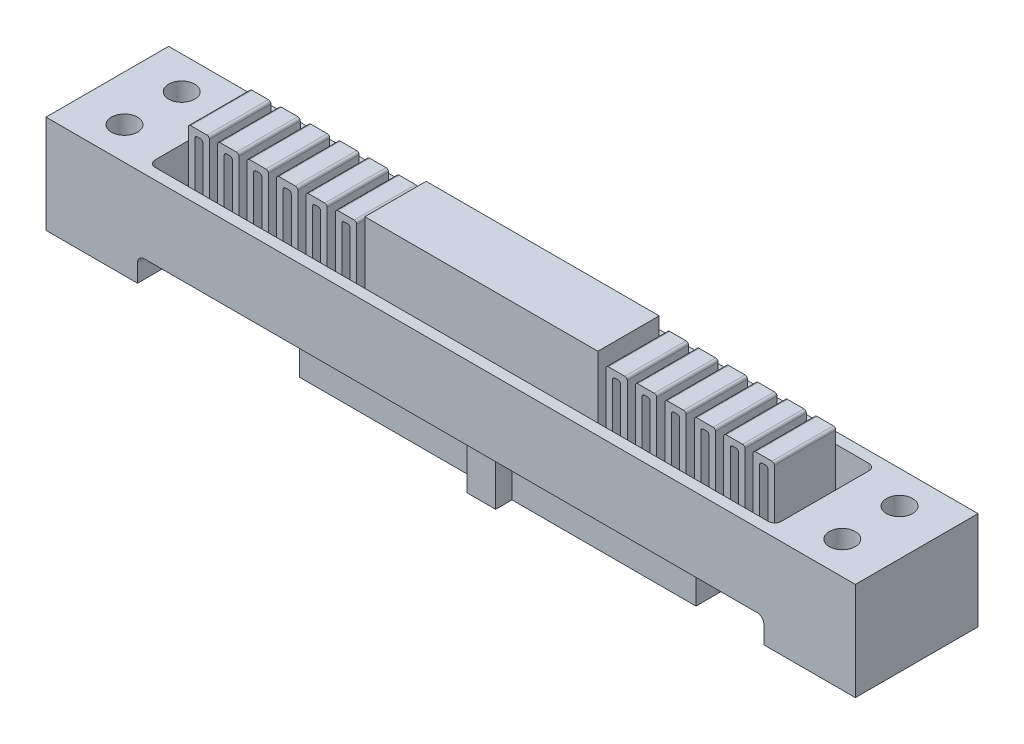
SolidWorks part; units mm, degrees
ref_plane "前视基准面" through (0, 0, 0) normal (0, 0, 1) x (1, 0, 0)
ref_plane "上视基准面" through (0, 0, 0) normal (0, 1, 0) x (1, 0, 0)
ref_plane "右视基准面" through (0, 0, 0) normal (1, 0, 0) x (0, 0, -1)
sketch "草图1" plane through (0, 0, 0) normal (0, 1, 0) x (1, 0, 0)
  line L0 (-1.75, 1.75) -> (-24.25, 1.75)
  line L1 (1.75, -3.75) -> (-1.75, -3.75)
  line L2 (1.75, -3.75) -> (1.75, -1.75)
  line L3 (1.75, 3.75) -> (-1.75, 3.75)
  line L4 (-1.75, -3.75) -> (-1.75, -1.75)
  line L5 (1.75, -3.75) -> (-1.75, 3.75) construction
  line L6 (1.75, 3.75) -> (-1.75, -3.75) construction
  line L7 (24.25, -1.75) -> (1.75, -1.75)
  line L8 (24.25, -1.75) -> (24.25, 1.75)
  line L9 (24.25, 1.75) -> (1.75, 1.75)
  line L10 (-24.25, -1.75) -> (-24.25, 1.75)
  line L11 (24.25, -1.75) -> (-24.25, 1.75) construction
  line L12 (24.25, 1.75) -> (-24.25, -1.75) construction
  line L13 (1.75, 1.75) -> (1.75, 3.75)
  line L14 (-1.75, -1.75) -> (-24.25, -1.75)
  line L15 (-1.75, 1.75) -> (-1.75, 3.75)
  point P0 (0, 0)
  point P6 (0, 0)
  dimension "D1" = 7.5
  dimension "D2" = 3.5
  dimension "D3" = 48.5
  dimension "D4" = 3.5
extrude "凸台-拉伸1" add sketch "草图1" along normal blind 23
ref_plane "基准面4" through (0, 5.8, 0) normal (0, -1, 0) x (-1, 0, 0)
ref_plane "基准面5" through (0, 8.8, 0) normal (0, -1, 0) x (-1, 0, 0)
sketch "草图3" plane through (0, 8.8, 0) normal (0, -1, 0) x (-1, 0, 0)
  line L0 (-14.25, 1.75) -> (-14.25, -1.75)
  line L1 (14.25, 1.75) -> (14.25, -1.75)
  line L12 (1.75, 1.75) -> (1.75, 3.75)
  line L13 (1.75, 3.75) -> (-1.75, 3.75)
  line L14 (-1.75, 3.75) -> (-1.75, 1.75)
  line L15 (-1.75, 1.75) -> (-24.25, 1.75)
  line L16 (-24.25, 1.75) -> (-24.25, -1.75)
  line L17 (-24.25, -1.75) -> (-1.75, -1.75)
  line L18 (-1.75, -1.75) -> (-1.75, -3.75)
  line L19 (-1.75, -3.75) -> (1.75, -3.75)
  line L20 (1.75, -3.75) -> (1.75, -1.75)
  line L21 (1.75, -1.75) -> (24.25, -1.75)
  line L22 (24.25, -1.75) -> (24.25, 1.75)
  line L23 (24.25, 1.75) -> (1.75, 1.75)
  line L27 (-14.25, 1.75) -> (-24.25, 1.75)
  line L28 (-24.25, 1.75) -> (-24.25, -1.75)
  line L29 (-24.25, -1.75) -> (-14.25, -1.75)
  line L33 (14.25, -1.75) -> (24.25, -1.75)
  line L34 (24.25, -1.75) -> (24.25, 1.75)
  line L35 (24.25, 1.75) -> (14.25, 1.75)
  dimension "D2" = 10
  dimension "D3" = 10
  dimension "D1" = 0
extrude "切除-拉伸1" cut sketch "草图3" against normal up to next
sketch "草图4" plane through (0, 0, 1.75) normal (0, 0, 1) x (1, 0, 0)
  line L0 (14.25, 11.2) -> (16.05, 11.2)
  line L1 (14.25, 23) -> (14.25, 8.8) construction
  line L2 (16.05, 11.2) -> (16.05, 21.2)
  line L3 (16.05, 21.2) -> (17.05, 21.2)
  line L4 (17.05, 21.2) -> (17.05, 11.2)
  line L5 (24.25, 8.8) -> (14.25, 8.8) construction
  line L6 (14.25, 12) -> (15.25, 12)
  line L7 (15.25, 12) -> (15.25, 22)
  line L8 (15.25, 22) -> (17.85, 22)
  line L9 (17.85, 22) -> (17.85, 12)
  line L10 (17.05, 11.2) -> (17.85, 11.2)
  line L11 (14.25, 12) -> (14.25, 11.2)
  line L12 (17.85, 22) -> (17.85, 11.2) construction
  line L13 (17.85, 11.2) -> (19.65, 11.2)
  line L14 (17.85, 12) -> (18.85, 12)
  line L15 (18.85, 12) -> (18.85, 22)
  line L16 (18.85, 22) -> (21.45, 22)
  line L17 (21.45, 22) -> (21.45, 12)
  line L18 (19.65, 21.2) -> (20.65, 21.2)
  line L19 (19.65, 11.2) -> (19.65, 21.2)
  line L20 (20.65, 21.2) -> (20.65, 11.2)
  line L21 (20.65, 11.2) -> (21.45, 11.2)
  line L22 (21.45, 11.2) -> (23.25, 11.2)
  line L23 (21.45, 12) -> (22.45, 12)
  line L24 (22.45, 12) -> (22.45, 22)
  line L25 (22.45, 22) -> (25.05, 22)
  line L26 (25.05, 22) -> (25.05, 12)
  line L27 (23.25, 21.2) -> (24.25, 21.2)
  line L28 (23.25, 11.2) -> (23.25, 21.2)
  line L29 (24.25, 21.2) -> (24.25, 11.2)
  line L30 (24.25, 11.2) -> (25.05, 11.2)
  line L31 (25.05, 11.2) -> (26.85, 11.2)
  line L32 (25.05, 12) -> (26.05, 12)
  line L33 (26.05, 12) -> (26.05, 22)
  line L34 (26.05, 22) -> (28.65, 22)
  line L35 (28.65, 22) -> (28.65, 12)
  line L36 (26.85, 21.2) -> (27.85, 21.2)
  line L37 (26.85, 11.2) -> (26.85, 21.2)
  line L38 (27.85, 21.2) -> (27.85, 11.2)
  line L39 (27.85, 11.2) -> (28.65, 11.2)
  line L40 (28.65, 11.2) -> (30.45, 11.2)
  line L41 (28.65, 12) -> (29.65, 12)
  line L42 (29.65, 12) -> (29.65, 22)
  line L43 (29.65, 22) -> (32.25, 22)
  line L44 (32.25, 22) -> (32.25, 12)
  line L45 (30.45, 21.2) -> (31.45, 21.2)
  line L46 (30.45, 11.2) -> (30.45, 21.2)
  line L47 (31.45, 21.2) -> (31.45, 11.2)
  line L48 (31.45, 11.2) -> (32.25, 11.2)
  line L49 (32.25, 11.2) -> (34.05, 11.2)
  line L50 (32.25, 12) -> (33.25, 12)
  line L51 (33.25, 12) -> (33.25, 22)
  line L52 (33.25, 22) -> (35.85, 22)
  line L53 (35.85, 22) -> (35.85, 12)
  line L54 (34.05, 21.2) -> (35.05, 21.2)
  line L55 (34.05, 11.2) -> (34.05, 21.2)
  line L56 (35.05, 21.2) -> (35.05, 11.2)
  line L57 (35.05, 11.2) -> (35.85, 11.2)
  line L58 (35.85, 11.2) -> (37.65, 11.2)
  line L59 (35.85, 12) -> (36.85, 12)
  line L60 (36.85, 12) -> (36.85, 22)
  line L61 (36.85, 22) -> (39.45, 22)
  line L62 (39.45, 22) -> (39.45, 12)
  line L63 (37.65, 21.2) -> (38.65, 21.2)
  line L64 (37.65, 11.2) -> (37.65, 21.2)
  line L65 (38.65, 21.2) -> (38.65, 11.2)
  line L66 (38.65, 11.2) -> (39.45, 11.2)
  line L67 (39.45, 11.2) -> (41.25, 11.2)
  line L68 (39.45, 12) -> (40.45, 12)
  line L69 (40.45, 12) -> (40.45, 22)
  line L70 (40.45, 22) -> (43.05, 22)
  line L71 (43.05, 22) -> (43.05, 12)
  line L72 (41.25, 21.2) -> (42.25, 21.2)
  line L73 (41.25, 11.2) -> (41.25, 21.2)
  line L74 (42.25, 21.2) -> (42.25, 11.2)
  line L75 (42.25, 11.2) -> (43.05, 11.2)
  line L76 (43.05, 11.2) -> (44.85, 11.2)
  line L77 (43.05, 12) -> (44.05, 12)
  line L78 (44.05, 12) -> (44.05, 22)
  line L79 (44.05, 22) -> (46.65, 22)
  line L80 (46.65, 22) -> (46.65, 12)
  line L81 (44.85, 21.2) -> (45.85, 21.2)
  line L82 (44.85, 11.2) -> (44.85, 21.2)
  line L83 (45.85, 21.2) -> (45.85, 11.2)
  line L84 (45.85, 11.2) -> (46.65, 11.2)
  line L85 (46.65, 11.2) -> (48.45, 11.2)
  line L86 (46.65, 12) -> (47.65, 12)
  line L87 (47.65, 12) -> (47.65, 22)
  line L88 (47.65, 22) -> (50.25, 22)
  line L89 (50.25, 22) -> (50.25, 12)
  line L90 (48.45, 21.2) -> (49.45, 21.2)
  line L91 (48.45, 11.2) -> (48.45, 21.2)
  line L92 (49.45, 21.2) -> (49.45, 11.2)
  line L93 (49.45, 11.2) -> (50.25, 11.2)
  line L94 (14.25, 11.2) -> (17.85, 11.2) construction
  line L95 (50.25, 11.2) -> (50.25, 12)
  dimension "D1" = 1.8
  dimension "D2" = 1
  dimension "D3" = 10
  dimension "D4" = 10
  dimension "D5" = 2.4
  dimension "D7" = 10
  dimension "D9" = 3.6
  dimension "D6" = 0.8
  dimension "D8" = 10
extrude "凸台-拉伸3" add sketch "草图4" against normal up to surface (3.5 mm away) contours L93 L95 L89 L88 L87 L86 L80 L79 L78 L77 L71 L70 L69 L68 L62 L61 L60 L59 L53 L52 L51 L50 L44 L43 L42 L41 L35 L34 L33 L32 L26 L25 L24 L23 L17 L16 L15 L14 L9 L8 L7 L6 L5 L0 L2 L3 L4 L10 L13 L19 L18 region at (14.6259, 11.6, 1.75) up to face at (13.4167, 10.6, -1.75)
fillet "圆角1" radius 0.3 78 edges at (45.85, 11.2, 0) (44.85, 11.2, 0) (42.25, 11.2, 0) (41.25, 11.2, 0) (38.65, 11.2, 0) (44.05, 12, 0) (40.45, 12, 0) (39.45, 12, 0) (43.05, 12, 0) (46.65, 12, 0) (47.65, 12, 0) (48.45, 11.2, 0) (48.45, 21.2, 0) (49.45, 21.2, 0) (45.85, 21.2, 0) (44.85, 21.2, 0) (41.25, 21.2, 0) (42.25, 21.2, 0) (38.65, 21.2, 0) (37.65, 21.2, 0) (50.25, 22, 0) (47.65, 22, 0) (46.65, 22, 0) (44.05, 22, 0) (43.05, 22, 0) (40.45, 22, 0) (39.45, 22, 0) (36.85, 22, 0) (37.65, 11.2, 0) (36.85, 12, 0) (35.85, 12, 0) (35.05, 11.2, 0) (35.05, 21.2, 0) (34.05, 21.2, 0) (35.85, 22, 0) (33.25, 22, 0) (33.25, 12, 0) (34.05, 11.2, 0) (32.25, 12, 0) (31.45, 11.2, 0) (31.45, 21.2, 0) (32.25, 22, 0) (30.45, 21.2, 0) (29.65, 22, 0) (29.65, 12, 0) (30.45, 11.2, 0) (28.65, 12, 0) (27.85, 11.2, 0) (27.85, 21.2, 0) (28.65, 22, 0) (26.85, 21.2, 0) (26.05, 22, 0) (26.05, 12, 0) (26.85, 11.2, 0) (25.05, 12, 0) (24.25, 11.2, 0) (24.25, 21.2, 0) (25.05, 22, 0) (22.45, 22, 0) (23.25, 21.2, 0) (23.25, 11.2, 0) (22.45, 12, 0) (20.65, 11.2, 0) (21.45, 12, 0) (21.45, 22, 0) (20.65, 21.2, 0) (19.65, 21.2, 0) (18.85, 22, 0) (19.65, 11.2, 0) (18.85, 12, 0) (17.85, 12, 0) (17.05, 11.2, 0) (16.05, 11.2, 0) (15.25, 12, 0) (17.05, 21.2, 0) (16.05, 21.2, 0) (17.85, 22, 0) (15.25, 22, 0)
mirror "镜向2" about plane through (0, 0, 0) normal (1, 0, 0) of "凸台-拉伸3", "圆角1"
fillet "圆角2" radius 0.3 4 edges at (-14.25, 12, 0) (-14.25, 11.2, 0) (14.25, 12, 0) (14.25, 11.2, 0)
ref_plane "基准面6" through (38.3, 0, 0) normal (1, 0, 0) x (0, 0, -1)
sketch "草图6" plane through (38.3, 0, 0) normal (1, 0, 0) x (0, 0, -1)
  line L0 (3.75, 23) -> (3.75, 0) construction
  line L1 (3.75, 0) -> (-3.75, 0)
  line L2 (3.75, 0) -> (3.75, 23)
  line L3 (3.75, 23) -> (-3.75, 23)
  line L4 (-3.75, 0) -> (-3.75, 23)
  dimension "D1" = 23
extrude "切除-拉伸2" cut sketch "草图6" along normal up to next
extrude "切除-拉伸3" cut sketch "草图6<2>" against normal blind 1.8
sketch "草图6<2>" plane through (38.3, 0, 0) normal (1, 0, 0) x (0, 0, -1) same geometry as "草图6"
sketch "草图7" plane through (36.5, 0, 0) normal (1, 0, 0) x (0, 0, -1)
  line L4 (1.75, 11.2) -> (1.75, 12)
  line L5 (1.75, 12) -> (-1.75, 12)
  line L6 (-1.75, 12) -> (-1.75, 11.2)
  line L7 (-1.75, 11.2) -> (1.75, 11.2)
  line L8 (1.75, 11.2) -> (1.75, 12)
  line L9 (1.75, 12) -> (-1.75, 12)
  line L10 (-1.75, 12) -> (-1.75, 11.2)
  line L11 (-1.75, 11.2) -> (1.75, 11.2)
  dimension "D1" = 0
extrude "凸台-拉伸4" add sketch "草图7" along normal up to surface (1.8 mm away) up to plane "基准面6"
mirror "镜向5" about plane through (0, 0, 0) normal (1, 0, 0) of "切除-拉伸3", "切除-拉伸2"
ref_plane "基准面7" through (-38.3, 0, 0) normal (-1, 0, 0) x (0, 0, 1)
sketch "草图16" plane through (-36.5, 0, 0) normal (-1, 0, 0) x (0, 0, 1)
  line L4 (-1.75, 11.2) -> (1.75, 11.2)
  line L5 (1.75, 11.2) -> (1.75, 12)
  line L6 (1.75, 12) -> (-1.75, 12)
  line L7 (-1.75, 12) -> (-1.75, 11.2)
  line L8 (-1.75, 11.2) -> (1.75, 11.2)
  line L9 (1.75, 11.2) -> (1.75, 12)
  line L10 (1.75, 12) -> (-1.75, 12)
  line L11 (-1.75, 12) -> (-1.75, 11.2)
  dimension "D1" = 0
extrude "凸台-拉伸8" add sketch "草图16" along normal up to surface (1.8 mm away) up to plane "基准面7"
sketch "草图12" plane through (0, 5.8, 0) normal (0, -1, 0) x (-1, 0, 0)
  line L0 (-24.25, -1.75) -> (-24.25, 1.75) construction
  line L1 (-49.5, -7.5) -> (-38.3, -7.5)
  line L2 (-49.5, -7.5) -> (-49.5, 7.5)
  line L3 (-49.5, 7.5) -> (-38.3, 7.5)
  line L4 (-38.3, -7.5) -> (-38.3, 7.5)
  line L5 (-49.5, -7.5) -> (-38.3, 7.5) construction
  line L6 (-49.5, 7.5) -> (-38.3, -7.5) construction
  point P0 (-43.9, 0)
  dimension "D1" = 14.05
  dimension "D2" = 11.2
  dimension "D3" = 15
extrude "凸台-拉伸7" add sketch "草图12" against normal blind 12
sketch "草图14" plane through (0, 17.8, 0) normal (0, 1, 0) x (1, 0, 0)
  line L0 (43.9, 7.5) -> (43.9, -7.5) construction
  line L1 (38.3, 7.5) -> (49.5, 7.5) construction
  line L2 (49.5, -7.5) -> (38.3, -7.5) construction
  circle A0 centre (43.9, 3.5) radius 1.6
  circle A1 centre (43.9, -3.5) radius 1.6
  dimension "D1" = 3.2
  dimension "D2" = 3.2
  dimension "D3" = 4
  dimension "D4" = 4
extrude "切除-拉伸5" cut sketch "草图14" against normal up to next
mirror "镜向7" about plane through (0, 0, 0) normal (1, 0, 0) of "切除-拉伸5", "凸台-拉伸7"
sketch "草图18" plane through (0, 0, 1.75) normal (0, 0, 1) x (1, 0, 0)
  line L0 (-14.25, 8.8) -> (-1.75, 8.8)
  line L58 (-36.15, 12) -> (-38.3, 12)
  line L59 (-38.3, 12) -> (-38.3, 11.2)
  line L60 (-38.3, 11.2) -> (-35.35, 11.2)
  line L61 (-35.05, 11.5) -> (-35.05, 20.9)
  line L62 (-34.75, 21.2) -> (-34.35, 21.2)
  line L63 (-34.05, 20.9) -> (-34.05, 11.5)
  line L64 (-33.75, 11.2) -> (-31.75, 11.2)
  line L65 (-31.45, 11.5) -> (-31.45, 20.9)
  line L66 (-31.15, 21.2) -> (-30.75, 21.2)
  line L67 (-30.45, 20.9) -> (-30.45, 11.5)
  line L68 (-30.15, 11.2) -> (-28.15, 11.2)
  line L69 (-27.85, 11.5) -> (-27.85, 20.9)
  line L70 (-27.55, 21.2) -> (-27.15, 21.2)
  line L71 (-26.85, 20.9) -> (-26.85, 11.5)
  line L72 (-26.55, 11.2) -> (-24.55, 11.2)
  line L73 (-24.25, 11.5) -> (-24.25, 20.9)
  line L74 (-23.95, 21.2) -> (-23.55, 21.2)
  line L75 (-23.25, 20.9) -> (-23.25, 11.5)
  line L76 (-22.95, 11.2) -> (-20.95, 11.2)
  line L77 (-20.65, 11.5) -> (-20.65, 20.9)
  line L78 (-20.35, 21.2) -> (-19.95, 21.2)
  line L79 (-19.65, 20.9) -> (-19.65, 11.5)
  line L80 (-19.35, 11.2) -> (-17.35, 11.2)
  line L81 (-17.05, 11.5) -> (-17.05, 20.9)
  line L82 (-16.75, 21.2) -> (-16.35, 21.2)
  line L83 (-16.05, 20.9) -> (-16.05, 11.5)
  line L84 (-15.75, 11.2) -> (-14.55, 11.2)
  line L85 (-14.25, 10.9) -> (-14.25, 8.8)
  line L86 (-14.25, 8.8) -> (-24.25, 8.8)
  line L87 (-24.25, 8.8) -> (-24.25, 0)
  line L88 (-24.25, 0) -> (-1.75, 0)
  line L89 (-1.75, 0) -> (-1.75, 23)
  line L90 (-1.75, 23) -> (-14.25, 23)
  line L91 (-14.25, 23) -> (-14.25, 12.3)
  line L92 (-14.55, 12) -> (-14.95, 12)
  line L93 (-15.25, 12.3) -> (-15.25, 21.7)
  line L94 (-15.55, 22) -> (-17.55, 22)
  line L95 (-17.85, 21.7) -> (-17.85, 12.3)
  line L96 (-18.15, 12) -> (-18.55, 12)
  line L97 (-18.85, 12.3) -> (-18.85, 21.7)
  line L98 (-19.15, 22) -> (-21.15, 22)
  line L99 (-21.45, 21.7) -> (-21.45, 12.3)
  line L100 (-21.75, 12) -> (-22.15, 12)
  line L101 (-22.45, 12.3) -> (-22.45, 21.7)
  line L102 (-22.75, 22) -> (-24.75, 22)
  line L103 (-25.05, 21.7) -> (-25.05, 12.3)
  line L104 (-25.35, 12) -> (-25.75, 12)
  line L105 (-26.05, 12.3) -> (-26.05, 21.7)
  line L106 (-26.35, 22) -> (-28.35, 22)
  line L107 (-28.65, 21.7) -> (-28.65, 12.3)
  line L108 (-28.95, 12) -> (-29.35, 12)
  line L109 (-29.65, 12.3) -> (-29.65, 21.7)
  line L110 (-29.95, 22) -> (-31.95, 22)
  line L111 (-32.25, 21.7) -> (-32.25, 12.3)
  line L112 (-32.55, 12) -> (-32.95, 12)
  line L113 (-33.25, 12.3) -> (-33.25, 21.7)
  line L114 (-33.55, 22) -> (-35.55, 22)
  line L115 (-35.85, 21.7) -> (-35.85, 12.3)
  line L116 (-36.15, 12) -> (-38.3, 12)
  line L117 (-38.3, 12) -> (-38.3, 11.2)
  line L118 (-38.3, 11.2) -> (-35.35, 11.2)
  line L119 (-35.05, 11.5) -> (-35.05, 20.9)
  line L120 (-34.75, 21.2) -> (-34.35, 21.2)
  line L121 (-34.05, 20.9) -> (-34.05, 11.5)
  line L122 (-33.75, 11.2) -> (-31.75, 11.2)
  line L123 (-31.45, 11.5) -> (-31.45, 20.9)
  line L124 (-31.15, 21.2) -> (-30.75, 21.2)
  line L125 (-30.45, 20.9) -> (-30.45, 11.5)
  line L126 (-30.15, 11.2) -> (-28.15, 11.2)
  line L127 (-27.85, 11.5) -> (-27.85, 20.9)
  line L128 (-27.55, 21.2) -> (-27.15, 21.2)
  line L129 (-26.85, 20.9) -> (-26.85, 11.5)
  line L130 (-26.55, 11.2) -> (-24.55, 11.2)
  line L131 (-24.25, 11.5) -> (-24.25, 20.9)
  line L132 (-23.95, 21.2) -> (-23.55, 21.2)
  line L133 (-23.25, 20.9) -> (-23.25, 11.5)
  line L134 (-22.95, 11.2) -> (-20.95, 11.2)
  line L135 (-20.65, 11.5) -> (-20.65, 20.9)
  line L136 (-20.35, 21.2) -> (-19.95, 21.2)
  line L137 (-19.65, 20.9) -> (-19.65, 11.5)
  line L138 (-19.35, 11.2) -> (-17.35, 11.2)
  line L139 (-17.05, 11.5) -> (-17.05, 20.9)
  line L140 (-16.75, 21.2) -> (-16.35, 21.2)
  line L141 (-16.05, 20.9) -> (-16.05, 11.5)
  line L142 (-15.75, 11.2) -> (-14.55, 11.2)
  line L143 (-14.25, 10.9) -> (-14.25, 8.8)
  line L147 (-1.75, 8.8) -> (-1.75, 23)
  line L148 (-1.75, 23) -> (-14.25, 23)
  line L149 (-14.25, 23) -> (-14.25, 12.3)
  line L150 (-14.55, 12) -> (-14.95, 12)
  line L151 (-15.25, 12.3) -> (-15.25, 21.7)
  line L152 (-15.55, 22) -> (-17.55, 22)
  line L153 (-17.85, 21.7) -> (-17.85, 12.3)
  line L154 (-18.15, 12) -> (-18.55, 12)
  line L155 (-18.85, 12.3) -> (-18.85, 21.7)
  line L156 (-19.15, 22) -> (-21.15, 22)
  line L157 (-21.45, 21.7) -> (-21.45, 12.3)
  line L158 (-21.75, 12) -> (-22.15, 12)
  line L159 (-22.45, 12.3) -> (-22.45, 21.7)
  line L160 (-22.75, 22) -> (-24.75, 22)
  line L161 (-25.05, 21.7) -> (-25.05, 12.3)
  line L162 (-25.35, 12) -> (-25.75, 12)
  line L163 (-26.05, 12.3) -> (-26.05, 21.7)
  line L164 (-26.35, 22) -> (-28.35, 22)
  line L165 (-28.65, 21.7) -> (-28.65, 12.3)
  line L166 (-28.95, 12) -> (-29.35, 12)
  line L167 (-29.65, 12.3) -> (-29.65, 21.7)
  line L168 (-29.95, 22) -> (-31.95, 22)
  line L169 (-32.25, 21.7) -> (-32.25, 12.3)
  line L170 (-32.55, 12) -> (-32.95, 12)
  line L171 (-33.25, 12.3) -> (-33.25, 21.7)
  line L172 (-33.55, 22) -> (-35.55, 22)
  line L173 (-35.85, 21.7) -> (-35.85, 12.3)
  arc A50 (-35.35, 11.2) -> (-35.05, 11.5) centre (-35.35, 11.5) ccw
  arc A51 (-34.75, 21.2) -> (-35.05, 20.9) centre (-34.75, 20.9) ccw
  arc A52 (-34.05, 20.9) -> (-34.35, 21.2) centre (-34.35, 20.9) ccw
  arc A53 (-34.05, 11.5) -> (-33.75, 11.2) centre (-33.75, 11.5) ccw
  arc A54 (-31.75, 11.2) -> (-31.45, 11.5) centre (-31.75, 11.5) ccw
  arc A55 (-31.15, 21.2) -> (-31.45, 20.9) centre (-31.15, 20.9) ccw
  arc A56 (-30.45, 20.9) -> (-30.75, 21.2) centre (-30.75, 20.9) ccw
  arc A57 (-30.45, 11.5) -> (-30.15, 11.2) centre (-30.15, 11.5) ccw
  arc A58 (-28.15, 11.2) -> (-27.85, 11.5) centre (-28.15, 11.5) ccw
  arc A59 (-27.55, 21.2) -> (-27.85, 20.9) centre (-27.55, 20.9) ccw
  arc A60 (-26.85, 20.9) -> (-27.15, 21.2) centre (-27.15, 20.9) ccw
  arc A61 (-26.85, 11.5) -> (-26.55, 11.2) centre (-26.55, 11.5) ccw
  arc A62 (-24.55, 11.2) -> (-24.25, 11.5) centre (-24.55, 11.5) ccw
  arc A63 (-23.95, 21.2) -> (-24.25, 20.9) centre (-23.95, 20.9) ccw
  arc A64 (-23.25, 20.9) -> (-23.55, 21.2) centre (-23.55, 20.9) ccw
  arc A65 (-23.25, 11.5) -> (-22.95, 11.2) centre (-22.95, 11.5) ccw
  arc A66 (-20.95, 11.2) -> (-20.65, 11.5) centre (-20.95, 11.5) ccw
  arc A67 (-20.35, 21.2) -> (-20.65, 20.9) centre (-20.35, 20.9) ccw
  arc A68 (-19.65, 20.9) -> (-19.95, 21.2) centre (-19.95, 20.9) ccw
  arc A69 (-19.65, 11.5) -> (-19.35, 11.2) centre (-19.35, 11.5) ccw
  arc A70 (-17.35, 11.2) -> (-17.05, 11.5) centre (-17.35, 11.5) ccw
  arc A71 (-16.75, 21.2) -> (-17.05, 20.9) centre (-16.75, 20.9) ccw
  arc A72 (-16.05, 20.9) -> (-16.35, 21.2) centre (-16.35, 20.9) ccw
  arc A73 (-16.05, 11.5) -> (-15.75, 11.2) centre (-15.75, 11.5) ccw
  arc A74 (-14.25, 10.9) -> (-14.55, 11.2) centre (-14.55, 10.9) ccw
  arc A75 (-14.55, 12) -> (-14.25, 12.3) centre (-14.55, 12.3) ccw
  arc A76 (-15.25, 12.3) -> (-14.95, 12) centre (-14.95, 12.3) ccw
  arc A77 (-15.25, 21.7) -> (-15.55, 22) centre (-15.55, 21.7) ccw
  arc A78 (-17.55, 22) -> (-17.85, 21.7) centre (-17.55, 21.7) ccw
  arc A79 (-18.15, 12) -> (-17.85, 12.3) centre (-18.15, 12.3) ccw
  arc A80 (-18.85, 12.3) -> (-18.55, 12) centre (-18.55, 12.3) ccw
  arc A81 (-18.85, 21.7) -> (-19.15, 22) centre (-19.15, 21.7) ccw
  arc A82 (-21.15, 22) -> (-21.45, 21.7) centre (-21.15, 21.7) ccw
  arc A83 (-21.75, 12) -> (-21.45, 12.3) centre (-21.75, 12.3) ccw
  arc A84 (-22.45, 12.3) -> (-22.15, 12) centre (-22.15, 12.3) ccw
  arc A85 (-22.45, 21.7) -> (-22.75, 22) centre (-22.75, 21.7) ccw
  arc A86 (-24.75, 22) -> (-25.05, 21.7) centre (-24.75, 21.7) ccw
  arc A87 (-25.35, 12) -> (-25.05, 12.3) centre (-25.35, 12.3) ccw
  arc A88 (-26.05, 12.3) -> (-25.75, 12) centre (-25.75, 12.3) ccw
  arc A89 (-26.05, 21.7) -> (-26.35, 22) centre (-26.35, 21.7) ccw
  arc A90 (-28.35, 22) -> (-28.65, 21.7) centre (-28.35, 21.7) ccw
  arc A91 (-28.95, 12) -> (-28.65, 12.3) centre (-28.95, 12.3) ccw
  arc A92 (-29.65, 12.3) -> (-29.35, 12) centre (-29.35, 12.3) ccw
  arc A93 (-29.65, 21.7) -> (-29.95, 22) centre (-29.95, 21.7) ccw
  arc A94 (-31.95, 22) -> (-32.25, 21.7) centre (-31.95, 21.7) ccw
  arc A95 (-32.55, 12) -> (-32.25, 12.3) centre (-32.55, 12.3) ccw
  arc A96 (-33.25, 12.3) -> (-32.95, 12) centre (-32.95, 12.3) ccw
  arc A97 (-33.25, 21.7) -> (-33.55, 22) centre (-33.55, 21.7) ccw
  arc A98 (-35.55, 22) -> (-35.85, 21.7) centre (-35.55, 21.7) ccw
  arc A99 (-36.15, 12) -> (-35.85, 12.3) centre (-36.15, 12.3) ccw
  arc A100 (-35.35, 11.2) -> (-35.05, 11.5) centre (-35.35, 11.5) ccw
  arc A101 (-34.75, 21.2) -> (-35.05, 20.9) centre (-34.75, 20.9) ccw
  arc A102 (-34.05, 20.9) -> (-34.35, 21.2) centre (-34.35, 20.9) ccw
  arc A103 (-34.05, 11.5) -> (-33.75, 11.2) centre (-33.75, 11.5) ccw
  arc A104 (-31.75, 11.2) -> (-31.45, 11.5) centre (-31.75, 11.5) ccw
  arc A105 (-31.15, 21.2) -> (-31.45, 20.9) centre (-31.15, 20.9) ccw
  arc A106 (-30.45, 20.9) -> (-30.75, 21.2) centre (-30.75, 20.9) ccw
  arc A107 (-30.45, 11.5) -> (-30.15, 11.2) centre (-30.15, 11.5) ccw
  arc A108 (-28.15, 11.2) -> (-27.85, 11.5) centre (-28.15, 11.5) ccw
  arc A109 (-27.55, 21.2) -> (-27.85, 20.9) centre (-27.55, 20.9) ccw
  arc A110 (-26.85, 20.9) -> (-27.15, 21.2) centre (-27.15, 20.9) ccw
  arc A111 (-26.85, 11.5) -> (-26.55, 11.2) centre (-26.55, 11.5) ccw
  arc A112 (-24.55, 11.2) -> (-24.25, 11.5) centre (-24.55, 11.5) ccw
  arc A113 (-23.95, 21.2) -> (-24.25, 20.9) centre (-23.95, 20.9) ccw
  arc A114 (-23.25, 20.9) -> (-23.55, 21.2) centre (-23.55, 20.9) ccw
  arc A115 (-23.25, 11.5) -> (-22.95, 11.2) centre (-22.95, 11.5) ccw
  arc A116 (-20.95, 11.2) -> (-20.65, 11.5) centre (-20.95, 11.5) ccw
  arc A117 (-20.35, 21.2) -> (-20.65, 20.9) centre (-20.35, 20.9) ccw
  arc A118 (-19.65, 20.9) -> (-19.95, 21.2) centre (-19.95, 20.9) ccw
  arc A119 (-19.65, 11.5) -> (-19.35, 11.2) centre (-19.35, 11.5) ccw
  arc A120 (-17.35, 11.2) -> (-17.05, 11.5) centre (-17.35, 11.5) ccw
  arc A121 (-16.75, 21.2) -> (-17.05, 20.9) centre (-16.75, 20.9) ccw
  arc A122 (-16.05, 20.9) -> (-16.35, 21.2) centre (-16.35, 20.9) ccw
  arc A123 (-16.05, 11.5) -> (-15.75, 11.2) centre (-15.75, 11.5) ccw
  arc A124 (-14.25, 10.9) -> (-14.55, 11.2) centre (-14.55, 10.9) ccw
  arc A125 (-14.55, 12) -> (-14.25, 12.3) centre (-14.55, 12.3) ccw
  arc A126 (-15.25, 12.3) -> (-14.95, 12) centre (-14.95, 12.3) ccw
  arc A127 (-15.25, 21.7) -> (-15.55, 22) centre (-15.55, 21.7) ccw
  arc A128 (-17.55, 22) -> (-17.85, 21.7) centre (-17.55, 21.7) ccw
  arc A129 (-18.15, 12) -> (-17.85, 12.3) centre (-18.15, 12.3) ccw
  arc A130 (-18.85, 12.3) -> (-18.55, 12) centre (-18.55, 12.3) ccw
  arc A131 (-18.85, 21.7) -> (-19.15, 22) centre (-19.15, 21.7) ccw
  arc A132 (-21.15, 22) -> (-21.45, 21.7) centre (-21.15, 21.7) ccw
  arc A133 (-21.75, 12) -> (-21.45, 12.3) centre (-21.75, 12.3) ccw
  arc A134 (-22.45, 12.3) -> (-22.15, 12) centre (-22.15, 12.3) ccw
  arc A135 (-22.45, 21.7) -> (-22.75, 22) centre (-22.75, 21.7) ccw
  arc A136 (-24.75, 22) -> (-25.05, 21.7) centre (-24.75, 21.7) ccw
  arc A137 (-25.35, 12) -> (-25.05, 12.3) centre (-25.35, 12.3) ccw
  arc A138 (-26.05, 12.3) -> (-25.75, 12) centre (-25.75, 12.3) ccw
  arc A139 (-26.05, 21.7) -> (-26.35, 22) centre (-26.35, 21.7) ccw
  arc A140 (-28.35, 22) -> (-28.65, 21.7) centre (-28.35, 21.7) ccw
  arc A141 (-28.95, 12) -> (-28.65, 12.3) centre (-28.95, 12.3) ccw
  arc A142 (-29.65, 12.3) -> (-29.35, 12) centre (-29.35, 12.3) ccw
  arc A143 (-29.65, 21.7) -> (-29.95, 22) centre (-29.95, 21.7) ccw
  arc A144 (-31.95, 22) -> (-32.25, 21.7) centre (-31.95, 21.7) ccw
  arc A145 (-32.55, 12) -> (-32.25, 12.3) centre (-32.55, 12.3) ccw
  arc A146 (-33.25, 12.3) -> (-32.95, 12) centre (-32.95, 12.3) ccw
  arc A147 (-33.25, 21.7) -> (-33.55, 22) centre (-33.55, 21.7) ccw
  arc A148 (-35.55, 22) -> (-35.85, 21.7) centre (-35.55, 21.7) ccw
  arc A149 (-36.15, 12) -> (-35.85, 12.3) centre (-36.15, 12.3) ccw
  dimension "D1" = 0
extrude "凸台-拉伸9" add sketch "草图18" along normal up to surface (2 mm away) up to face at (0, 11.5, 3.75)
sketch "草图19" plane through (0, 0, -1.75) normal (0, 0, -1) x (-1, 0, 0)
  line L0 (14.25, 8.8) -> (1.75, 8.8)
  line L1 (-4.125, 8.8) -> (4.125, 8.8) construction
  line L58 (35.35, 11.2) -> (38.3, 11.2)
  line L59 (38.3, 11.2) -> (38.3, 12)
  line L60 (38.3, 12) -> (36.15, 12)
  line L61 (35.85, 12.3) -> (35.85, 21.7)
  line L62 (35.55, 22) -> (33.55, 22)
  line L63 (33.25, 21.7) -> (33.25, 12.3)
  line L64 (32.95, 12) -> (32.55, 12)
  line L65 (32.25, 12.3) -> (32.25, 21.7)
  line L66 (31.95, 22) -> (29.95, 22)
  line L67 (29.65, 21.7) -> (29.65, 12.3)
  line L68 (29.35, 12) -> (28.95, 12)
  line L69 (28.65, 12.3) -> (28.65, 21.7)
  line L70 (28.35, 22) -> (26.35, 22)
  line L71 (26.05, 21.7) -> (26.05, 12.3)
  line L72 (25.75, 12) -> (25.35, 12)
  line L73 (25.05, 12.3) -> (25.05, 21.7)
  line L74 (24.75, 22) -> (22.75, 22)
  line L75 (22.45, 21.7) -> (22.45, 12.3)
  line L76 (22.15, 12) -> (21.75, 12)
  line L77 (21.45, 12.3) -> (21.45, 21.7)
  line L78 (21.15, 22) -> (19.15, 22)
  line L79 (18.85, 21.7) -> (18.85, 12.3)
  line L80 (18.55, 12) -> (18.15, 12)
  line L81 (17.85, 12.3) -> (17.85, 21.7)
  line L82 (17.55, 22) -> (15.55, 22)
  line L83 (15.25, 21.7) -> (15.25, 12.3)
  line L84 (14.95, 12) -> (14.55, 12)
  line L85 (14.25, 12.3) -> (14.25, 23)
  line L86 (14.25, 23) -> (1.75, 23)
  line L87 (1.75, 23) -> (1.75, 0)
  line L88 (1.75, 0) -> (24.25, 0)
  line L89 (24.25, 0) -> (24.25, 8.8)
  line L90 (24.25, 8.8) -> (14.25, 8.8)
  line L91 (14.25, 8.8) -> (14.25, 10.9)
  line L92 (14.55, 11.2) -> (15.75, 11.2)
  line L93 (16.05, 11.5) -> (16.05, 20.9)
  line L94 (16.35, 21.2) -> (16.75, 21.2)
  line L95 (17.05, 20.9) -> (17.05, 11.5)
  line L96 (17.35, 11.2) -> (19.35, 11.2)
  line L97 (19.65, 11.5) -> (19.65, 20.9)
  line L98 (19.95, 21.2) -> (20.35, 21.2)
  line L99 (20.65, 20.9) -> (20.65, 11.5)
  line L100 (20.95, 11.2) -> (22.95, 11.2)
  line L101 (23.25, 11.5) -> (23.25, 20.9)
  line L102 (23.55, 21.2) -> (23.95, 21.2)
  line L103 (24.25, 20.9) -> (24.25, 11.5)
  line L104 (24.55, 11.2) -> (26.55, 11.2)
  line L105 (26.85, 11.5) -> (26.85, 20.9)
  line L106 (27.15, 21.2) -> (27.55, 21.2)
  line L107 (27.85, 20.9) -> (27.85, 11.5)
  line L108 (28.15, 11.2) -> (30.15, 11.2)
  line L109 (30.45, 11.5) -> (30.45, 20.9)
  line L110 (30.75, 21.2) -> (31.15, 21.2)
  line L111 (31.45, 20.9) -> (31.45, 11.5)
  line L112 (31.75, 11.2) -> (33.75, 11.2)
  line L113 (34.05, 11.5) -> (34.05, 20.9)
  line L114 (34.35, 21.2) -> (34.75, 21.2)
  line L115 (35.05, 20.9) -> (35.05, 11.5)
  line L116 (35.35, 11.2) -> (38.3, 11.2)
  line L117 (38.3, 11.2) -> (38.3, 12)
  line L118 (38.3, 12) -> (36.15, 12)
  line L119 (35.85, 12.3) -> (35.85, 21.7)
  line L120 (35.55, 22) -> (33.55, 22)
  line L121 (33.25, 21.7) -> (33.25, 12.3)
  line L122 (32.95, 12) -> (32.55, 12)
  line L123 (32.25, 12.3) -> (32.25, 21.7)
  line L124 (31.95, 22) -> (29.95, 22)
  line L125 (29.65, 21.7) -> (29.65, 12.3)
  line L126 (29.35, 12) -> (28.95, 12)
  line L127 (28.65, 12.3) -> (28.65, 21.7)
  line L128 (28.35, 22) -> (26.35, 22)
  line L129 (26.05, 21.7) -> (26.05, 12.3)
  line L130 (25.75, 12) -> (25.35, 12)
  line L131 (25.05, 12.3) -> (25.05, 21.7)
  line L132 (24.75, 22) -> (22.75, 22)
  line L133 (22.45, 21.7) -> (22.45, 12.3)
  line L134 (22.15, 12) -> (21.75, 12)
  line L135 (21.45, 12.3) -> (21.45, 21.7)
  line L136 (21.15, 22) -> (19.15, 22)
  line L137 (18.85, 21.7) -> (18.85, 12.3)
  line L138 (18.55, 12) -> (18.15, 12)
  line L139 (17.85, 12.3) -> (17.85, 21.7)
  line L140 (17.55, 22) -> (15.55, 22)
  line L141 (15.25, 21.7) -> (15.25, 12.3)
  line L142 (14.95, 12) -> (14.55, 12)
  line L143 (14.25, 12.3) -> (14.25, 23)
  line L144 (14.25, 23) -> (1.75, 23)
  line L145 (1.75, 23) -> (1.75, 8.8)
  line L149 (14.25, 8.8) -> (14.25, 10.9)
  line L150 (14.55, 11.2) -> (15.75, 11.2)
  line L151 (16.05, 11.5) -> (16.05, 20.9)
  line L152 (16.35, 21.2) -> (16.75, 21.2)
  line L153 (17.05, 20.9) -> (17.05, 11.5)
  line L154 (17.35, 11.2) -> (19.35, 11.2)
  line L155 (19.65, 11.5) -> (19.65, 20.9)
  line L156 (19.95, 21.2) -> (20.35, 21.2)
  line L157 (20.65, 20.9) -> (20.65, 11.5)
  line L158 (20.95, 11.2) -> (22.95, 11.2)
  line L159 (23.25, 11.5) -> (23.25, 20.9)
  line L160 (23.55, 21.2) -> (23.95, 21.2)
  line L161 (24.25, 20.9) -> (24.25, 11.5)
  line L162 (24.55, 11.2) -> (26.55, 11.2)
  line L163 (26.85, 11.5) -> (26.85, 20.9)
  line L164 (27.15, 21.2) -> (27.55, 21.2)
  line L165 (27.85, 20.9) -> (27.85, 11.5)
  line L166 (28.15, 11.2) -> (30.15, 11.2)
  line L167 (30.45, 11.5) -> (30.45, 20.9)
  line L168 (30.75, 21.2) -> (31.15, 21.2)
  line L169 (31.45, 20.9) -> (31.45, 11.5)
  line L170 (31.75, 11.2) -> (33.75, 11.2)
  line L171 (34.05, 11.5) -> (34.05, 20.9)
  line L172 (34.35, 21.2) -> (34.75, 21.2)
  line L173 (35.05, 20.9) -> (35.05, 11.5)
  arc A50 (35.85, 12.3) -> (36.15, 12) centre (36.15, 12.3) ccw
  arc A51 (35.85, 21.7) -> (35.55, 22) centre (35.55, 21.7) ccw
  arc A52 (33.55, 22) -> (33.25, 21.7) centre (33.55, 21.7) ccw
  arc A53 (32.95, 12) -> (33.25, 12.3) centre (32.95, 12.3) ccw
  arc A54 (32.25, 12.3) -> (32.55, 12) centre (32.55, 12.3) ccw
  arc A55 (32.25, 21.7) -> (31.95, 22) centre (31.95, 21.7) ccw
  arc A56 (29.95, 22) -> (29.65, 21.7) centre (29.95, 21.7) ccw
  arc A57 (29.35, 12) -> (29.65, 12.3) centre (29.35, 12.3) ccw
  arc A58 (28.65, 12.3) -> (28.95, 12) centre (28.95, 12.3) ccw
  arc A59 (28.65, 21.7) -> (28.35, 22) centre (28.35, 21.7) ccw
  arc A60 (26.35, 22) -> (26.05, 21.7) centre (26.35, 21.7) ccw
  arc A61 (25.75, 12) -> (26.05, 12.3) centre (25.75, 12.3) ccw
  arc A62 (25.05, 12.3) -> (25.35, 12) centre (25.35, 12.3) ccw
  arc A63 (25.05, 21.7) -> (24.75, 22) centre (24.75, 21.7) ccw
  arc A64 (22.75, 22) -> (22.45, 21.7) centre (22.75, 21.7) ccw
  arc A65 (22.15, 12) -> (22.45, 12.3) centre (22.15, 12.3) ccw
  arc A66 (21.45, 12.3) -> (21.75, 12) centre (21.75, 12.3) ccw
  arc A67 (21.45, 21.7) -> (21.15, 22) centre (21.15, 21.7) ccw
  arc A68 (19.15, 22) -> (18.85, 21.7) centre (19.15, 21.7) ccw
  arc A69 (18.55, 12) -> (18.85, 12.3) centre (18.55, 12.3) ccw
  arc A70 (17.85, 12.3) -> (18.15, 12) centre (18.15, 12.3) ccw
  arc A71 (17.85, 21.7) -> (17.55, 22) centre (17.55, 21.7) ccw
  arc A72 (15.55, 22) -> (15.25, 21.7) centre (15.55, 21.7) ccw
  arc A73 (14.95, 12) -> (15.25, 12.3) centre (14.95, 12.3) ccw
  arc A74 (14.25, 12.3) -> (14.55, 12) centre (14.55, 12.3) ccw
  arc A75 (14.55, 11.2) -> (14.25, 10.9) centre (14.55, 10.9) ccw
  arc A76 (15.75, 11.2) -> (16.05, 11.5) centre (15.75, 11.5) ccw
  arc A77 (16.35, 21.2) -> (16.05, 20.9) centre (16.35, 20.9) ccw
  arc A78 (17.05, 20.9) -> (16.75, 21.2) centre (16.75, 20.9) ccw
  arc A79 (17.05, 11.5) -> (17.35, 11.2) centre (17.35, 11.5) ccw
  arc A80 (19.35, 11.2) -> (19.65, 11.5) centre (19.35, 11.5) ccw
  arc A81 (19.95, 21.2) -> (19.65, 20.9) centre (19.95, 20.9) ccw
  arc A82 (20.65, 20.9) -> (20.35, 21.2) centre (20.35, 20.9) ccw
  arc A83 (20.65, 11.5) -> (20.95, 11.2) centre (20.95, 11.5) ccw
  arc A84 (22.95, 11.2) -> (23.25, 11.5) centre (22.95, 11.5) ccw
  arc A85 (23.55, 21.2) -> (23.25, 20.9) centre (23.55, 20.9) ccw
  arc A86 (24.25, 20.9) -> (23.95, 21.2) centre (23.95, 20.9) ccw
  arc A87 (24.25, 11.5) -> (24.55, 11.2) centre (24.55, 11.5) ccw
  arc A88 (26.55, 11.2) -> (26.85, 11.5) centre (26.55, 11.5) ccw
  arc A89 (27.15, 21.2) -> (26.85, 20.9) centre (27.15, 20.9) ccw
  arc A90 (27.85, 20.9) -> (27.55, 21.2) centre (27.55, 20.9) ccw
  arc A91 (27.85, 11.5) -> (28.15, 11.2) centre (28.15, 11.5) ccw
  arc A92 (30.15, 11.2) -> (30.45, 11.5) centre (30.15, 11.5) ccw
  arc A93 (30.75, 21.2) -> (30.45, 20.9) centre (30.75, 20.9) ccw
  arc A94 (31.45, 20.9) -> (31.15, 21.2) centre (31.15, 20.9) ccw
  arc A95 (31.45, 11.5) -> (31.75, 11.2) centre (31.75, 11.5) ccw
  arc A96 (33.75, 11.2) -> (34.05, 11.5) centre (33.75, 11.5) ccw
  arc A97 (34.35, 21.2) -> (34.05, 20.9) centre (34.35, 20.9) ccw
  arc A98 (35.05, 20.9) -> (34.75, 21.2) centre (34.75, 20.9) ccw
  arc A99 (35.05, 11.5) -> (35.35, 11.2) centre (35.35, 11.5) ccw
  arc A100 (35.85, 12.3) -> (36.15, 12) centre (36.15, 12.3) ccw
  arc A101 (35.85, 21.7) -> (35.55, 22) centre (35.55, 21.7) ccw
  arc A102 (33.55, 22) -> (33.25, 21.7) centre (33.55, 21.7) ccw
  arc A103 (32.95, 12) -> (33.25, 12.3) centre (32.95, 12.3) ccw
  arc A104 (32.25, 12.3) -> (32.55, 12) centre (32.55, 12.3) ccw
  arc A105 (32.25, 21.7) -> (31.95, 22) centre (31.95, 21.7) ccw
  arc A106 (29.95, 22) -> (29.65, 21.7) centre (29.95, 21.7) ccw
  arc A107 (29.35, 12) -> (29.65, 12.3) centre (29.35, 12.3) ccw
  arc A108 (28.65, 12.3) -> (28.95, 12) centre (28.95, 12.3) ccw
  arc A109 (28.65, 21.7) -> (28.35, 22) centre (28.35, 21.7) ccw
  arc A110 (26.35, 22) -> (26.05, 21.7) centre (26.35, 21.7) ccw
  arc A111 (25.75, 12) -> (26.05, 12.3) centre (25.75, 12.3) ccw
  arc A112 (25.05, 12.3) -> (25.35, 12) centre (25.35, 12.3) ccw
  arc A113 (25.05, 21.7) -> (24.75, 22) centre (24.75, 21.7) ccw
  arc A114 (22.75, 22) -> (22.45, 21.7) centre (22.75, 21.7) ccw
  arc A115 (22.15, 12) -> (22.45, 12.3) centre (22.15, 12.3) ccw
  arc A116 (21.45, 12.3) -> (21.75, 12) centre (21.75, 12.3) ccw
  arc A117 (21.45, 21.7) -> (21.15, 22) centre (21.15, 21.7) ccw
  arc A118 (19.15, 22) -> (18.85, 21.7) centre (19.15, 21.7) ccw
  arc A119 (18.55, 12) -> (18.85, 12.3) centre (18.55, 12.3) ccw
  arc A120 (17.85, 12.3) -> (18.15, 12) centre (18.15, 12.3) ccw
  arc A121 (17.85, 21.7) -> (17.55, 22) centre (17.55, 21.7) ccw
  arc A122 (15.55, 22) -> (15.25, 21.7) centre (15.55, 21.7) ccw
  arc A123 (14.95, 12) -> (15.25, 12.3) centre (14.95, 12.3) ccw
  arc A124 (14.25, 12.3) -> (14.55, 12) centre (14.55, 12.3) ccw
  arc A125 (14.55, 11.2) -> (14.25, 10.9) centre (14.55, 10.9) ccw
  arc A126 (15.75, 11.2) -> (16.05, 11.5) centre (15.75, 11.5) ccw
  arc A127 (16.35, 21.2) -> (16.05, 20.9) centre (16.35, 20.9) ccw
  arc A128 (17.05, 20.9) -> (16.75, 21.2) centre (16.75, 20.9) ccw
  arc A129 (17.05, 11.5) -> (17.35, 11.2) centre (17.35, 11.5) ccw
  arc A130 (19.35, 11.2) -> (19.65, 11.5) centre (19.35, 11.5) ccw
  arc A131 (19.95, 21.2) -> (19.65, 20.9) centre (19.95, 20.9) ccw
  arc A132 (20.65, 20.9) -> (20.35, 21.2) centre (20.35, 20.9) ccw
  arc A133 (20.65, 11.5) -> (20.95, 11.2) centre (20.95, 11.5) ccw
  arc A134 (22.95, 11.2) -> (23.25, 11.5) centre (22.95, 11.5) ccw
  arc A135 (23.55, 21.2) -> (23.25, 20.9) centre (23.55, 20.9) ccw
  arc A136 (24.25, 20.9) -> (23.95, 21.2) centre (23.95, 20.9) ccw
  arc A137 (24.25, 11.5) -> (24.55, 11.2) centre (24.55, 11.5) ccw
  arc A138 (26.55, 11.2) -> (26.85, 11.5) centre (26.55, 11.5) ccw
  arc A139 (27.15, 21.2) -> (26.85, 20.9) centre (27.15, 20.9) ccw
  arc A140 (27.85, 20.9) -> (27.55, 21.2) centre (27.55, 20.9) ccw
  arc A141 (27.85, 11.5) -> (28.15, 11.2) centre (28.15, 11.5) ccw
  arc A142 (30.15, 11.2) -> (30.45, 11.5) centre (30.15, 11.5) ccw
  arc A143 (30.75, 21.2) -> (30.45, 20.9) centre (30.75, 20.9) ccw
  arc A144 (31.45, 20.9) -> (31.15, 21.2) centre (31.15, 20.9) ccw
  arc A145 (31.45, 11.5) -> (31.75, 11.2) centre (31.75, 11.5) ccw
  arc A146 (33.75, 11.2) -> (34.05, 11.5) centre (33.75, 11.5) ccw
  arc A147 (34.35, 21.2) -> (34.05, 20.9) centre (34.35, 20.9) ccw
  arc A148 (35.05, 20.9) -> (34.75, 21.2) centre (34.75, 20.9) ccw
  arc A149 (35.05, 11.5) -> (35.35, 11.2) centre (35.35, 11.5) ccw
  dimension "D1" = 0
extrude "凸台-拉伸10" add sketch "草图19" along normal up to surface (2 mm away) up to face at (0, 11.5, -3.75)
mirror "镜向9" about plane through (0, 0, 0) normal (1, 0, 0) of "凸台-拉伸10", "凸台-拉伸9"
fillet "圆角3" radius 0.6 8 edges at (8, 8.8, -3.75) (8, 8.8, -1.75) (-8, 8.8, -3.75) (-8, 8.8, -1.75) (8, 8.8, 3.75) (-8, 8.8, 3.75) (8, 8.8, 1.75) (-8, 8.8, 1.75)
fillet "圆角4" radius 0.6 2 edges at (-14.25, 8.8, 0) (14.25, 8.8, 0)
fillet "圆角5" radius 1.2 8 edges at (-38.3, 12, 0) (-38.3, 11.6, -3.75) (-38.3, 11.2, 0) (-38.3, 11.6, 3.75) (38.3, 11.6, 3.75) (38.3, 11.2, 0) (38.3, 11.6, -3.75) (38.3, 12, 0)
sketch "草图20" plane through (38.3, 0, 0) normal (-1, 0, 0) x (0, 0, 1)
  line L0 (-4.95, 10) -> (-4.95, 13.2) construction
  line L1 (-7.5, 17.8) -> (-6.15, 17.8)
  line L2 (-7.5, 17.8) -> (-7.5, 8.8)
  line L3 (-7.5, 8.8) -> (-6.15, 8.8)
  line L4 (-6.15, 17.8) -> (-6.15, 8.8)
  line L5 (7.5, 5.8) -> (-7.5, 5.8) construction
  dimension "D1" = 1.2
  dimension "D2" = 3
extrude "凸台-拉伸11" add sketch "草图20" along normal up to next
mirror "镜向10" about plane through (0, 0, 0) normal (0, 0, 1) of "凸台-拉伸11"
fillet "圆角6" radius 0.8 8 edges at (-38.3, 8.8, 6.825) (-38.3, 13.3, 6.15) (-38.3, 8.8, -6.825) (-38.3, 13.3, -6.15) (38.3, 8.8, 6.825) (38.3, 8.8, -6.825) (38.3, 13.3, -6.15) (38.3, 13.3, 6.15)
